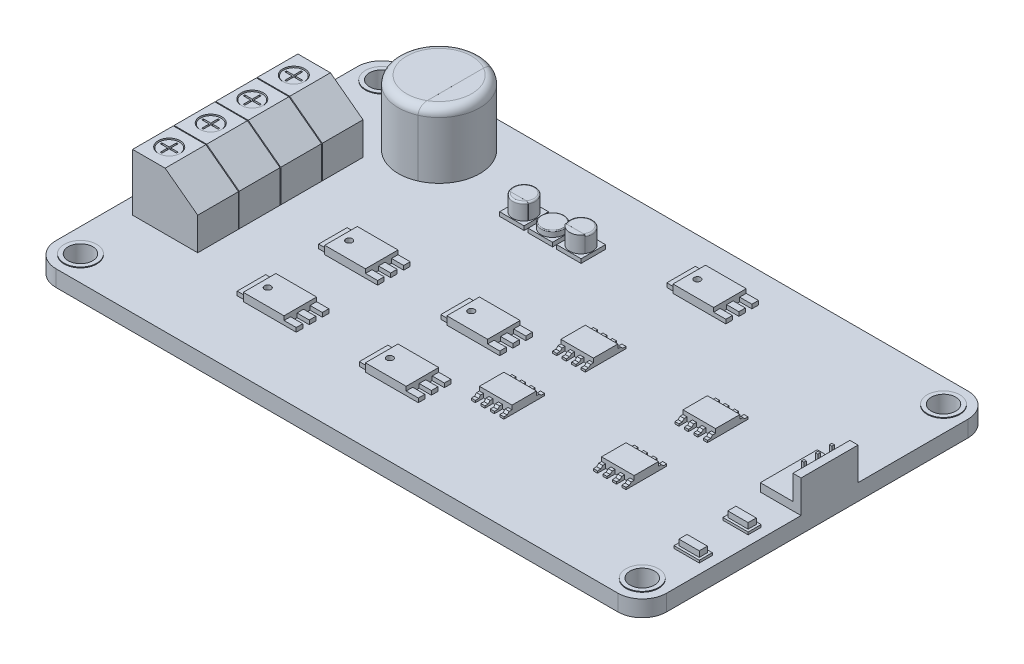
SolidWorks part; units mm, degrees
ref_plane "Front Plane" through (0, 0, 0) normal (0, 0, 1) x (1, 0, 0)
ref_plane "Top Plane" through (0, 0, 0) normal (0, 1, 0) x (1, 0, 0)
ref_plane "Right Plane" through (0, 0, 0) normal (1, 0, 0) x (0, 0, -1)
sketch "Sketch1" plane through (0, 0, 0) normal (0, 1, 0) x (1, 0, 0)
  line L1 (34.5, -21.5) -> (-34.5, -21.5)
  line L2 (37.5, -18.5) -> (37.5, 18.5)
  line L3 (34.5, 21.5) -> (-34.5, 21.5)
  line L4 (-37.5, -18.5) -> (-37.5, 18.5)
  line L5 (37.5, -21.5) -> (-37.5, 21.5) construction
  line L6 (37.5, 21.5) -> (-37.5, -21.5) construction
  circle A0 centre (-34.5, 18.5) radius 1.5
  circle A1 centre (34.5, 18.5) radius 1.5
  circle A2 centre (34.5, -18.5) radius 1.5
  circle A3 centre (-34.5, -18.5) radius 1.5
  arc A4 (-34.5, -21.5) -> (-37.5, -18.5) centre (-34.5, -18.5) cw
  arc A5 (34.5, -21.5) -> (37.5, -18.5) centre (34.5, -18.5) ccw
  arc A6 (-34.5, 21.5) -> (-37.5, 18.5) centre (-34.5, 18.5) ccw
  arc A7 (37.5, 18.5) -> (34.5, 21.5) centre (34.5, 18.5) ccw
  point P0 (0, 0)
  dimension "D3" = 3
  dimension "D8" = 3
  dimension "D1" = 75
  dimension "D2" = 43
  dimension "D4" = 37
  dimension "D5" = 18.5
  dimension "D6" = 69
  dimension "D7" = 34.5
extrude "Boss-Extrude1" add sketch "Sketch1" along normal blind 2
ref_plane "Plane1" through (0, 0, 1) normal (0, 0, 1) x (1, 0, 0)
sketch "Sketch8" plane through (0, 0, 1) normal (0, 0, 1) x (1, 0, 0)
  line L0 (-35.5, 2) -> (-35.5, 9)
  line L1 (-34.5, 2) -> (34.5, 2) construction
  line L2 (-35.5, 9) -> (-31.5, 9)
  line L3 (-31.5, 9) -> (-27.5, 6)
  line L4 (-27.5, 6) -> (-27.5, 2)
  line L5 (-27.5, 2) -> (-35.5, 2)
  line L6 (-37.5, 2) -> (-37.5, 0) construction
  dimension "D1" = 2
  dimension "D2" = 7
  dimension "D3" = 8
  dimension "D4" = 4
  dimension "D5" = 4
extrude "Boss-Extrude3" add sketch "Sketch8" along normal blind 5
sketch "Sketch9" plane through (0, 9, 0) normal (0, 1, 0) x (1, 0, 0)
  line L0 (-31.5, -1) -> (-35.5, -1) construction
  line L1 (-35.5, -6) -> (-35.5, -1) construction
  line L2 (-33.5, -3.5) -> (-33.5, -2.5)
  line L3 (-33.4, -4.5) -> (-33.4, -3.5)
  line L4 (-33.5, -4.5) -> (-33.5, -3.5)
  line L5 (-32.5, -3.5) -> (-34.5, -3.5)
  line L6 (-33.4, -3.5) -> (-33.4, -2.5)
  line L7 (-32.5, -3.4) -> (-34.5, -3.4)
  line L8 (-33.6, -4.5) -> (-33.6, -3.5)
  line L9 (-33.6, -3.5) -> (-33.6, -2.5)
  line L10 (-32.5, -3.6) -> (-34.5, -3.6)
  line L11 (-33.6, -2.5) -> (-33.4, -2.5)
  line L12 (-32.5, -3.4) -> (-32.5, -3.6)
  line L13 (-33.4, -4.5) -> (-33.6, -4.5)
  line L14 (-34.5, -3.6) -> (-34.5, -3.4)
  circle A0 centre (-33.5, -3.5) radius 1.25
  circle A1 centre (-33.5, -3.5) radius 1.35
  dimension "D1" = 2.5
  dimension "D2" = 2.5
  dimension "D3" = 2
  dimension "D5" = 1
  dimension "D6" = 1
  dimension "D7" = 1
  dimension "D8" = 1
  dimension "D4" = 0.1
  dimension "D9" = 0.1
  dimension "D10" = 0.1
extrude "Cut-Extrude2" cut sketch "Sketch9" against normal blind 2.5 contours A1 A0 region at (-34.8118, 9, 3.5)
extrude "Cut-Extrude4" cut sketch "Sketch9<4>" against normal blind 0.1 contours A0
sketch "Sketch9<4>" plane through (0, 9, 0) normal (0, 1, 0) x (1, 0, 0) same geometry as "Sketch9"
extrude "Cut-Extrude3" cut sketch "Sketch9<3>" against normal blind 0.5 contours L11 L2 L7 L6 | L11 L9 L7 L2 | L13 L3 L10 L4 | L13 L4 L10 L8 | L7 L14 L10 L12 region at (-33.55, 9, 2.95) region at (-33.45, 9, 2.95) region at (-33.45, 9, 4.05) region at (-33.55, 9, 4.05)
sketch "Sketch9<3>" plane through (0, 9, 0) normal (0, 1, 0) x (1, 0, 0) same geometry as "Sketch9"
pattern_linear "LPattern1" count 2 spacing 5.1 along (0, 0, 1) count 3 spacing 5.1 along (0, 0, -1) of "Boss-Extrude3", "Cut-Extrude2", "Cut-Extrude4", "Cut-Extrude3" pattern seed only yes
sketch "Sketch10" plane through (0, 2, 0) normal (0, 1, 0) x (1, 0, 0)
  circle A0 centre (-34.5, 18.5) radius 1.5 construction
  circle A11 centre (-34.5, 18.5) radius 2
  circle A12 centre (-34.5, 18.5) radius 2
  circle A14 centre (34.5, 18.5) radius 2
  circle A15 centre (34.5, 18.5) radius 2
  circle A17 centre (34.5, -18.5) radius 2
  circle A18 centre (34.5, -18.5) radius 2
  circle A19 centre (-34.5, -18.5) radius 1.5
  circle A20 centre (-34.5, -18.5) radius 2
  circle A21 centre (-34.5, -18.5) radius 2
  circle A22 centre (-34.5, 18.5) radius 1.5
  circle A23 centre (34.5, 18.5) radius 1.5
  circle A24 centre (34.5, -18.5) radius 1.5
  dimension "D1" = 0.5
  dimension "D2" = 0.5
  dimension "D3" = 0.5
  dimension "D4" = 0.5
extrude "Boss-Extrude4" add sketch "Sketch10" along normal blind 0.1
sketch "Sketch11" plane through (0, 2, 0) normal (0, 1, 0) x (1, 0, 0)
  circle A0 centre (-23.5927, 14.6414) radius 5
  dimension "D2" = 10
extrude "Boss-Extrude5" add sketch "Sketch11" along normal blind 8
fillet "Fillet1" radius 1 1 edges at (-23.5927, 10, -9.6414)
sketch "Sketch12" plane through (0, 2, 0) normal (0, 1, 0) x (1, 0, 0)
  line L0 (-37.5, 18.5) -> (-37.5, -18.5) construction
  line L1 (-19.5, -3.5) -> (-14.5, -3.5)
  line L2 (-19.5, -3.5) -> (-19.5, 0.5)
  line L3 (-19.5, 0.5) -> (-14.5, 0.5)
  line L4 (-14.5, -3.5) -> (-14.5, 0.5)
  line L5 (-34.5, -21.5) -> (34.5, -21.5) construction
  line L6 (-14.5, -3.5) -> (-13, -3.5)
  line L7 (-13, -3.5) -> (-13, -2.7)
  line L8 (-13, -2.7) -> (-14.5, -2.7)
  line L9 (-14.5, -1.901) -> (-13, -1.901)
  line L10 (-13, -1.901) -> (-13, -1.101)
  line L11 (-13, -1.101) -> (-14.5, -1.101)
  line L12 (-14.5, 0.5) -> (-13, 0.5)
  line L13 (-13, 0.5) -> (-13, -0.301)
  line L14 (-13, -0.301) -> (-14.5, -0.301)
  circle A0 centre (-18.5, -1.5) radius 0.4
  point P21 (-19.5, -1.5)
  dimension "D10" = 0.8
  dimension "D1" = 4
  dimension "D2" = 5
  dimension "D3" = 18
  dimension "D4" = 18
  dimension "D5" = 0.8
  dimension "D6" = 0.8
  dimension "D7" = 0.801
  dimension "D8" = 0.8
  dimension "D9" = 1.5
  dimension "D11" = 1
extrude "Boss-Extrude6" add sketch "Sketch12" along normal blind 1 contours L1 L4 L3 L2 region at (-16.9613, 2, 1.5)
extrude "Boss-Extrude7" add sketch "Sketch12<3>" along normal blind 0.5 contours L14 L13 L12 L4 | L10 L11 L4 L9 | L7 L8 L4 L6 region at (-13.75, 2, 3.1) region at (-13.75, 2, -0.0995) region at (-13.75, 2, 1.501)
sketch "Sketch12<3>" plane through (0, 2, 0) normal (0, 1, 0) x (1, 0, 0) same geometry as "Sketch12"
sketch "Sketch13" plane through (-19.5, 0, 0) normal (-1, 0, 0) x (0, 0, 1)
  line L0 (3.5, 2) -> (-0.5, 2) construction
  line L1 (-0.25, 2) -> (3.25, 2)
  line L2 (-0.25, 2) -> (-0.25, 2.5025)
  line L3 (-0.25, 2.5025) -> (3.25, 2.5025)
  line L4 (3.25, 2) -> (3.25, 2.5025)
  line L5 (3.5, 3) -> (-0.5, 3) construction
  point P6 (1.5, 2.5025)
  point P9 (1.5, 3)
  dimension "D1" = 0.5025
  dimension "D2" = 3.5
extrude "Boss-Extrude8" add sketch "Sketch13" along normal blind 1
pattern_linear "LPattern3" count 2 spacing 10 along (0, 0, 1) count 2 spacing 15 along (1, 0, 0) of "Boss-Extrude6", "Boss-Extrude7", "Boss-Extrude8"
sketch "Sketch14" plane through (0, 10, 0) normal (0, 1, 0) x (1, 0, 0)
  line L0 (-21.5927, 19.2239) -> (-21.5927, 10.0588)
  circle A0 centre (-23.5927, 14.6414) radius 5
  circle M4 centre (-23.5927, 14.6414) radius 4
  dimension "D1" = 10
  dimension "D2" = 3
extrude "Cut-Extrude5" cut sketch "Sketch14" against normal up to surface (8 mm away) contours L0 M4 | L0 A0 M4 region at (-19.4901, 10, -17.3272) region at (-20.7726, 10, -14.6414) up to face at (-15.9375, 2, 11.5004)
sketch "Sketch15" plane through (0, 2, 0) normal (0, 1, 0) x (1, 0, 0)
  line L0 (-21.5917, 19.2235) -> (-21.5917, 10.0588)
  line L3 (-21.5927, 19.2239) -> (-21.5927, 10.0588) construction
  circle A0 centre (-23.5927, 14.6414) radius 5
  dimension "D1" = 10
  dimension "D3" = 0.001
extrude "Boss-Extrude9" add sketch "Sketch15" along normal up to surface (8 mm away) contours L0 A0 region at (-20.3547, 2, -14.6414) up to face at (-24.5927, 10, -14.6414)
fillet "Fillet2" radius 1 1 edges at (-18.5927, 10, -14.6414)
sketch "Sketch16" plane through (0, 2, 0) normal (0, 1, 0) x (1, 0, 0)
  line L0 (6, 13.767) -> (11, 13.767)
  line L1 (6, 13.767) -> (6, 17.767)
  line L2 (6, 17.767) -> (11, 17.767)
  line L3 (11, 13.767) -> (11, 17.767)
  line L4 (11, 17.767) -> (12.5, 17.767)
  line L5 (12.5, 17.767) -> (12.5, 16.967)
  line L6 (12.5, 16.967) -> (11, 16.967)
  line L7 (11, 16.167) -> (12.5, 16.167)
  line L8 (12.5, 16.167) -> (12.5, 15.367)
  line L9 (12.5, 15.367) -> (11, 15.367)
  line L10 (11, 13.767) -> (12.5, 13.767)
  line L11 (12.5, 13.767) -> (12.5, 14.567)
  line L12 (12.5, 14.567) -> (11, 14.567)
  circle A0 centre (7, 15.767) radius 0.4
  point P5 (6, 15.767)
  dimension "D9" = 0.8
  dimension "D1" = 4
  dimension "D2" = 5
  dimension "D3" = 0.8
  dimension "D4" = 1.5
  dimension "D5" = 0.8
  dimension "D6" = 0.8
  dimension "D7" = 0.8
  dimension "D8" = 6
  dimension "D10" = 1
extrude "Boss-Extrude10" add sketch "Sketch16" along normal blind 1 contours L0 L3 L2 L1 region at (8.5387, 2, -15.767)
extrude "Boss-Extrude11" add sketch "Sketch16<3>" along normal blind 0.5 contours L6 L5 L4 L3 | L9 L8 L7 L3 | L11 L12 L3 L10 region at (11.75, 2, -14.167) region at (11.75, 2, -17.367) region at (11.75, 2, -15.767)
sketch "Sketch16<3>" plane through (0, 2, 0) normal (0, 1, 0) x (1, 0, 0) same geometry as "Sketch16"
sketch "Sketch17" plane through (6, 0, 0) normal (-1, 0, 0) x (0, 0, 1)
  line L0 (-13.767, 2) -> (-17.767, 2) construction
  line L1 (-17.517, 2) -> (-14.017, 2)
  line L2 (-17.517, 2) -> (-17.517, 2.5)
  line L3 (-17.517, 2.5) -> (-14.017, 2.5)
  line L4 (-14.017, 2) -> (-14.017, 2.5)
  line L5 (-13.767, 3) -> (-17.767, 3) construction
  point P6 (-15.767, 2.5)
  point P9 (-15.767, 3)
  dimension "D1" = 0.5
  dimension "D2" = 3.5
extrude "Boss-Extrude12" add sketch "Sketch17" along normal blind 1
sketch "Sketch18" plane through (0, 2, 0) normal (0, 1, 0) x (1, 0, 0)
  line L0 (5, 4) -> (5, 5)
  line L1 (5, 4) -> (9, 4)
  line L2 (5, 4) -> (5, 1)
  line L3 (5, 1) -> (9, 1)
  line L4 (9, 4) -> (9, 1)
  line L5 (5, 5) -> (5.5, 5)
  line L6 (5.5, 5) -> (5.5, 4)
  line L7 (6.1633, 4) -> (6.1633, 5)
  line L8 (6.1633, 5) -> (6.6633, 5)
  line L9 (6.6633, 5) -> (6.6633, 4)
  line L10 (7.3333, 4) -> (7.3333, 5)
  line L11 (7.3333, 5) -> (7.8333, 5)
  line L12 (7.8333, 5) -> (7.8333, 4)
  line L13 (8.5, 4) -> (8.5, 5)
  line L14 (8.5, 5) -> (9, 5)
  line L15 (9, 5) -> (9, 4)
  line L16 (9, 1) -> (9, 0)
  line L17 (9, 0) -> (8.5, 0)
  line L18 (8.5, 0) -> (8.5, 1)
  line L19 (7.8333, 1) -> (7.8333, 0)
  line L20 (7.8333, 0) -> (7.3333, 0)
  line L21 (7.3333, 0) -> (7.3333, 1)
  line L22 (6.6633, 1) -> (6.6633, 0)
  line L23 (6.6633, 0) -> (6.1633, 0)
  line L24 (6.1633, 0) -> (6.1633, 1)
  line L25 (5, 1) -> (5, 0)
  line L26 (5, 0) -> (5.5, 0)
  line L27 (5.5, 0) -> (5.5, 1)
  dimension "D1" = 3
  dimension "D2" = 4
  dimension "D3" = 0.5
  dimension "D4" = 0.5
  dimension "D5" = 0.6667
  dimension "D6" = 0.67
  dimension "D7" = 0.5
  dimension "D8" = 0.5
  dimension "D9" = 1
  dimension "D10" = 5
  dimension "D11" = 4
extrude "Boss-Extrude13" add sketch "Sketch18" along normal blind 1 contours L4 L1 L2 L3 region at (7, 2, -2.5)
extrude "Boss-Extrude14" add sketch "Sketch18<3>" along normal blind 0.5 contours L18 L17 L16 L3 | L21 L20 L19 L3 | L24 L23 L22 L3 | L26 L27 L3 L25 | L15 L14 L13 L1 | L12 L11 L10 L1 | L9 L8 L7 L1 | L6 L5 L0 L1 region at (5.25, 2, -4.5) region at (5.25, 2, -0.5) region at (6.4133, 2, -4.5) region at (6.4133, 2, -0.5) region at (7.5833, 2, -4.5) region at (7.5833, 2, -0.5) region at (8.75, 2, -4.5) region at (8.75, 2, -0.5)
sketch "Sketch18<3>" plane through (0, 2, 0) normal (0, 1, 0) x (1, 0, 0) same geometry as "Sketch18"
sketch "Sketch19" plane through (9, 0, 0) normal (1, 0, 0) x (0, 0, -1)
  line L0 (-18.5, 2) -> (18.5, 2) construction
  line L1 (0, 2.5) -> (1, 2.5)
  line L2 (0, 2.5) -> (0, 2)
  line L3 (0, 2) -> (1, 2)
  line L4 (1, 2.5) -> (1, 2)
  line L5 (1, 2.5) -> (0.6524, 2.5)
  line L6 (0.6524, 2.5) -> (0.4024, 2.25)
  line L7 (0.4024, 2.25) -> (0, 2.25)
  line L8 (2.5, 3) -> (2.5, 2) construction
  line L9 (4, 3) -> (1, 3) construction
  line L10 (5, 2) -> (0, 2) construction
  line L11 (4.5976, 2.25) -> (5, 2.25)
  line L12 (4.3476, 2.5) -> (4.5976, 2.25)
  line L13 (5, 2) -> (4, 2)
  line L14 (4, 2.5) -> (4, 2)
  line L15 (5, 2.5) -> (4, 2.5)
  line L16 (5, 2.5) -> (5, 2)
  line M9 (5, 2) -> (5, 2.5)
  line M10 (5, 2.5) -> (4, 2.5)
  line M15 (0, 2.5) -> (0, 2)
  dimension "D1" = 0.25
  dimension "D2" = 0.3476
extrude "Cut-Extrude6" cut sketch "Sketch19" against normal up to surface (4 mm away) contours L7 L6 L1 M15 | L12 L11 M10 M9 region at (9, 2.3849, -0.2686) region at (9, 2.3849, -4.7314)
pattern_linear "LPattern4" count 2 spacing 10 along (0, 0, 1) count 2 spacing 15 along (1, 0, 0) of "Boss-Extrude13", "Cut-Extrude6", "Boss-Extrude14"
sketch "Sketch20" plane through (0, 2, 0) normal (0, 1, 0) x (1, 0, 0)
  line L1 (-12.825, 14.3088) -> (-9.825, 14.3088)
  line L2 (-12.825, 14.3088) -> (-12.825, 11.3088)
  line L3 (-12.825, 11.3088) -> (-9.825, 11.3088)
  line L4 (-9.825, 14.3088) -> (-9.825, 11.3088)
  dimension "D1" = 3
  dimension "D2" = 3
extrude "Boss-Extrude15" add sketch "Sketch20" along normal blind 0.5
pattern_linear "LPattern5" count 3 spacing 3.5 along (1, 0, 0) of "Boss-Extrude15"
sketch "Sketch21" plane through (0, 2.5, 0) normal (0, 1, 0) x (1, 0, 0)
  line L0 (-9.825, 14.3088) -> (-12.825, 14.3088) construction
  line L1 (-12.825, 14.3088) -> (-12.825, 11.3088) construction
  circle A0 centre (-11.325, 12.8088) radius 1.4
  point P6 (-11.325, 14.3088)
  point P10 (-12.825, 12.8088)
  dimension "D1" = 2.8
extrude "Boss-Extrude16" add sketch "Sketch21" along normal blind 2
sketch "Sketch22" plane through (0, 4.5, 0) normal (0, 1, 0) x (1, 0, 0)
  line L0 (-12.5375, 12.1088) -> (-10.1126, 12.1088)
  circle A0 centre (-11.325, 12.8088) radius 1.4
  circle M3 centre (-11.325, 12.8088) radius 1.4
  dimension "D1" = 2.8
  dimension "D2" = 0.7
extrude "Cut-Extrude7" cut sketch "Sketch22" against normal up to surface (2 mm away) contours L0 M3 region at (-11.325, 4.5, -11.8217) up to face at (-11.325, 2.5, -11.4088)
sketch "Sketch23" plane through (0, 4.5, 0) normal (0, 1, 0) x (1, 0, 0)
  line L0 (-12.5369, 12.1078) -> (-10.1132, 12.1078)
  line L1 (-12.5375, 12.1088) -> (-10.1126, 12.1088) construction
  circle A0 centre (-11.325, 12.8088) radius 1.4
  dimension "D1" = 2.8
  dimension "D2" = 0.001
extrude "Boss-Extrude17" add sketch "Sketch23" against normal up to surface (2 mm away) contours L0 A0 region at (-11.325, 4.5, -11.8212) up to face at (-11.325, 2.5, -13.1588)
fillet "Fillet3" radius 0.2 1 edges at (-11.325, 4.5, -11.4088)
fillet "Fillet4" radius 0.2 1 edges at (-11.325, 4.5, -14.2088)
pattern_linear "LPattern6" count 2 spacing 7 along (1, 0, 0) of "Boss-Extrude16", "Boss-Extrude17", "Fillet4", "Cut-Extrude7"
sketch "Sketch24" plane through (0, 2.5, 0) normal (0, 1, 0) x (1, 0, 0)
  line L0 (-6.325, 14.3088) -> (-9.325, 14.3088) construction
  line L1 (-9.325, 14.3088) -> (-9.325, 11.3088) construction
  circle A0 centre (-7.825, 12.8088) radius 1.4
  point P5 (-7.825, 14.3088)
  point P9 (-9.325, 12.8088)
  dimension "D1" = 2.8
extrude "Boss-Extrude18" add sketch "Sketch24" along normal blind 0.7
fillet "Fillet5" radius 0.1 1 edges at (-7.825, 3.2, -11.4088)
sketch "Sketch25" plane through (0, 2, 0) normal (0, 1, 0) x (1, 0, 0)
  line L0 (37.5, -18.5) -> (37.5, 18.5) construction
  line L1 (32.5, 5) -> (37.5, 5)
  line L2 (32.5, 5) -> (32.5, -2)
  line L3 (32.5, -2) -> (37.5, -2)
  line L4 (37.5, 5) -> (37.5, -2)
  line L5 (34.5, 21.5) -> (-34.5, 21.5) construction
  dimension "D1" = 7
  dimension "D2" = 5
  dimension "D3" = 16.5
extrude "Boss-Extrude19" add sketch "Sketch25" along normal blind 1
sketch "Sketch26" plane through (0, 3, 0) normal (0, 1, 0) x (1, 0, 0)
  line L0 (32.5, -2) -> (37.5, -2) construction
  line L1 (37.5, 5) -> (36.5, 5)
  line L2 (37.5, 5) -> (37.5, -2)
  line L3 (37.5, -2) -> (36.5, -2)
  line L4 (36.5, 5) -> (36.5, -2)
  dimension "D1" = 1
extrude "Boss-Extrude20" add sketch "Sketch26" along normal blind 3
sketch "Sketch27" plane through (0, 3, 0) normal (0, 1, 0) x (1, 0, 0)
  line L0 (36.5, 5) -> (36.5, -2) construction
  line L1 (35.7, 3.58) -> (36, 3.58)
  line L2 (35.7, 3.58) -> (35.7, 3.28)
  line L3 (35.7, 3.28) -> (36, 3.28)
  line L4 (36, 3.58) -> (36, 3.28)
  line L5 (36.5, 5) -> (32.5, 5) construction
  line L6 (35.7, 1.8633) -> (35.7, 1.5633)
  line L7 (35.7, 1.8633) -> (36, 1.8633)
  line L8 (36, 1.8633) -> (36, 1.5633)
  line L9 (35.7, 1.5633) -> (36, 1.5633)
  line L10 (35.7, 0.1467) -> (35.7, -0.1533)
  line L11 (35.7, 0.1467) -> (36, 0.1467)
  line L12 (36, 0.1467) -> (36, -0.1533)
  line L13 (35.7, -0.1533) -> (36, -0.1533)
  dimension "D1" = 0.3
  dimension "D2" = 0.5
  dimension "D3" = 1.42
  dimension "D5" = 1.4167
  dimension "D4" = 3
extrude "Boss-Extrude21" add sketch "Sketch27" along normal blind 3
sketch "Sketch28" plane through (0, 2, 0) normal (0, 1, 0) x (1, 0, 0)
  line L0 (32.5, -2) -> (36.5, -2) construction
  line L1 (33.5, -6) -> (36, -6)
  line L2 (33.5, -6) -> (33.5, -7)
  line L3 (33.5, -7) -> (36, -7)
  line L4 (36, -6) -> (36, -7)
  line L5 (37.5, -18.5) -> (37.5, -2) construction
  dimension "D1" = 4
  dimension "D2" = 1
  dimension "D3" = 2.5
  dimension "D4" = 1.5
extrude "Boss-Extrude22" add sketch "Sketch28" along normal blind 1
sketch "Sketch29" plane through (0, 2, 0) normal (0, 1, 0) x (1, 0, 0)
  line L8 (33.2, -5.7) -> (33.2, -7.3)
  line L9 (33.2, -7.3) -> (36.3, -7.3)
  line L10 (36.3, -7.3) -> (36.3, -5.7)
  line L11 (36.3, -5.7) -> (33.2, -5.7)
  line L12 (33.2, -5.7) -> (33.2, -7.3)
  line L13 (33.2, -7.3) -> (36.3, -7.3)
  line L14 (36.3, -7.3) -> (36.3, -5.7)
  line L15 (36.3, -5.7) -> (33.2, -5.7)
  dimension "D1" = 0.3
extrude "Boss-Extrude23" add sketch "Sketch29" along normal blind 0.3
pattern_linear "LPattern7" count 2 spacing 6 along (0, 0, 1) of "Boss-Extrude23", "Boss-Extrude22"
